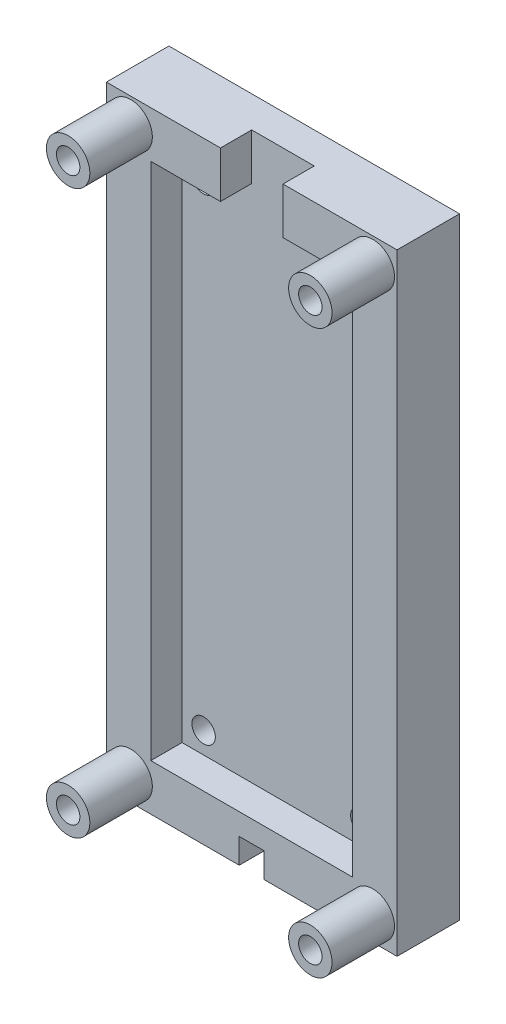
SolidWorks part; units mm, degrees
ref_plane "Front Plane" through (0, 0, 0) normal (0, 0, 1) x (1, 0, 0)
ref_plane "Top Plane" through (0, 0, 0) normal (0, 1, 0) x (1, 0, 0)
ref_plane "Right Plane" through (0, 0, 0) normal (1, 0, 0) x (0, 0, -1)
sketch "Sketch2" plane through (0, 0, 0) normal (0, 0, 1) x (1, 0, 0)
  line L0 (-7.1, -7.425) -> (-7.1, 90.475)
  line L1 (0, 0) -> (32.3, 0)
  line L2 (0, 0) -> (0, 83.05)
  line L3 (0, 83.05) -> (32.3, 83.05)
  line L4 (32.3, 0) -> (32.3, 83.05)
  line L5 (0, 0) -> (32.3, 83.05) construction
  line L6 (0, 83.05) -> (32.3, 0) construction
  line L7 (-7.1, 90.475) -> (39.4, 90.475)
  line L8 (39.4, -7.425) -> (39.4, 90.475)
  line L9 (-7.1, -7.425) -> (39.4, -7.425)
  line L10 (16.15, 3.425) -> (16.15, 79.625) construction
  line L11 (3.45, 79.625) -> (28.85, 79.625)
  line L12 (3.45, 79.625) -> (3.45, 3.425)
  line L13 (3.45, 3.425) -> (28.85, 3.425)
  line L14 (28.85, 79.625) -> (28.85, 3.425)
  line L15 (3.45, 79.625) -> (28.85, 3.425) construction
  line L16 (3.45, 3.425) -> (28.85, 79.625) construction
  line L17 (16.15, 0) -> (16.15, -7.425) construction
  line L18 (0, 41.525) -> (-7.1, 41.525) construction
  point P4 (16.15, 41.525)
  point P10 (16.15, 41.525)
  dimension "D1" = 83.05
  dimension "D2" = 32.3
  dimension "D4" = 25.4
  dimension "D5" = 76.2
  dimension "D3" = 46.5
  dimension "D6" = 97.9
extrude "Boss-Extrude1" add sketch "Sketch2" along normal mid plane 10 contours L0 L9 L8 L7 L4 L1 L2 L3 region at (-6.0162, 41.525, 0)
extrude "Boss-Extrude2" add sketch "Sketch2<4>" against normal blind 5 contours L14 L11 L12 L13 | L1 L4 L3 L2 L11 L14 L13 L12 region at (0.8911, 41.525, 0) region at (16.15, 41.525, 0)
sketch "Sketch2<4>" plane through (0, 0, 0) normal (0, 0, 1) x (1, 0, 0) same geometry as "Sketch2"
ref_axis "Axis1" through (16.15, 3.425, 0) along (0, 1, 0)
sketch "Sketch3" plane through (-7.1, 0, 0) normal (-1, 0, 0) x (0, 0, 1)
  line L0 (-5, -7.425) -> (-5, 90.475) construction
  line L1 (-5, 76.725) -> (5, 76.725)
  line L2 (-5, 76.725) -> (-5, 74.225)
  line L3 (-5, 74.225) -> (5, 74.225)
  line L4 (5, 76.725) -> (5, 74.225)
  line L5 (-5, 76.725) -> (5, 74.225) construction
  line L6 (-5, 74.225) -> (5, 76.725) construction
  line L7 (5, -7.425) -> (5, 90.475) construction
  line L8 (-5, 41.525) -> (5, 41.525) construction
  line L9 (-5, 8.825) -> (5, 8.825)
  line L10 (5, 6.325) -> (5, 8.825)
  line L11 (-5, 6.325) -> (5, 6.325)
  line L12 (-5, 6.325) -> (-5, 8.825)
  line L14 (5, 90.475) -> (-5, 90.475) construction
  point P4 (0, 75.475)
  dimension "D1" = 2.5
  dimension "D2" = 15
extrude "Boss-Extrude3" [suppressed] add sketch "Sketch3" along normal blind 2.5
ref_plane "Plane1" through (16.15, 0, 0) normal (-1, 0, 0) x (0, 0, 1)
chamfer "Chamfer1" [suppressed] distance 0.5 angle 45
mirror "Mirror2" [suppressed] about plane through (16.15, 0, 0) normal (-1, 0, 0)
sketch "Sketch4" plane through (0, 0, 0) normal (0, 0, 1) x (1, 0, 0)
  point P0 (3.45, 79.625)
  point P3 (28.85, 79.625)
  point P6 (3.45, 3.425)
  point P9 (28.85, 3.425)
hole_wizard "Tap Drill for M3x0.5 Tap1" positions "Sketch4" profile "Sketch5" hole size "M3x0.5" standard "ANSI Metric" end condition through all
sketch "Sketch5" plane through (3.45, 79.625, 0) normal (1, 0, 0) x (0, -1, 0)
  line L0 (0, 0) -> (0, 5)
  line L1 (0, 5) -> (1.875, 5)
  line L2 (1.875, 5) -> (1.875, 0)
  line L5 (1.875, 0) -> (0, 0)
  line L11 (0, -6.35) -> (0, 107.95) construction
  dimension "Thru Hole Dia." = 3.75
  dimension "Thru Hole Depth" = 5
sketch "Sketch7" plane through (0, 0, 0) normal (0, 0, 1) x (1, 0, 0)
  line L0 (16.15, 5.5) -> (16.15, -5.5) construction
  line L1 (-3.225, 86.525) -> (35.525, 86.525)
  line L2 (-3.225, 86.525) -> (-3.225, -3.475)
  line L3 (-3.225, -3.475) -> (35.525, -3.475)
  line L4 (35.525, 86.525) -> (35.525, -3.475)
  line L5 (16.15, -3.475) -> (16.15, 86.525) construction
  line L6 (-3.225, 41.525) -> (35.525, 41.525) construction
  line L7 (9.5243, 83.05) -> (9.5243, 86.525) construction
  line L8 (0, 83.05) -> (32.3, 83.05) construction
  line L9 (9.5243, -3.475) -> (9.5243, 0) construction
  line L10 (0, 0) -> (32.3, 0) construction
  circle A0 centre (-3.225, 86.525) radius 1.875
  circle A1 centre (35.525, 86.525) radius 1.875
  circle A2 centre (35.525, -3.475) radius 1.875
  circle A3 centre (-3.225, -3.475) radius 1.875
  circle A4 centre (-3.225, 86.525) radius 3.475
  circle A5 centre (35.525, 86.525) radius 3.475
  circle A6 centre (-3.225, -3.475) radius 3.475
  circle A7 centre (35.525, -3.475) radius 3.475
  point P480 (16.15, 41.525)
  dimension "D4" = 3.75
  dimension "D1" = 38.75
  dimension "D2" = 90
  dimension "D3" = 9.5243
  dimension "D5" = 1.6
extrude "Boss-Extrude5" add sketch "Sketch7" along normal blind 15 contours L2 A6 L3 A3 | L3 A6 L2 A3 | A4 | A0 | A5 | A1 | A2 | A7 region at (-1.4713, -1.7213, 0) region at (-3.3233, -0.8, 0)
sketch "Sketch6" plane through (0, 90.475, 0) normal (0, 1, 0) x (1, 0, 0)
  line L4 (-12.2839, -5.4418) -> (-12.3348, -5.4418)
  line L5 (44.5642, -5.5441) -> (44.6151, -5.5441)
  arc A0 (44.6151, -5.5441) -> (-12.3348, -5.4418) centre (16.15, 0) cw
  arc A1 (44.5642, -5.5441) -> (-12.2839, -5.4418) centre (16.15, 0) cw
  arc A2 (44.566, -5.5346) -> (-12.2857, -5.4325) centre (16.15, 0) cw construction
  dimension "D1" = 29
  dimension "D2" = 0.05
extrude "Boss-Extrude4" add sketch "Sketch6" against normal blind 97.55 separate body
extrude "Cut-Extrude1" cut sketch "Sketch6<2>" against normal through all both and the other way through all
sketch "Sketch6<2>" plane through (0, 90.475, 0) normal (0, 1, 0) x (1, 0, 0) same geometry as "Sketch6"
sketch "Sketch11" plane through (0, 0, 5) normal (0, 0, 1) x (1, 0, 0)
  line L0 (0, 83.05) -> (32.3, 83.05) construction
  line L1 (11.15, 75.55) -> (21.15, 75.55)
  line L2 (11.15, 75.55) -> (11.15, 90.55)
  line L3 (11.15, 90.55) -> (21.15, 90.55)
  line L4 (21.15, 75.55) -> (21.15, 90.55)
  line L5 (11.15, 75.55) -> (21.15, 90.55) construction
  line L6 (11.15, 90.55) -> (21.15, 75.55) construction
  point P0 (16.15, 83.05)
  dimension "D1" = 10
  dimension "D2" = 15
extrude "Cut-Extrude2" cut sketch "Sketch11" against normal up to surface (5 mm away) and the other way through all up to face at (5.325, 79.625, 0)
sketch "Sketch12" plane through (0, 0, 5) normal (0, 0, 1) x (1, 0, 0)
  line L0 (-7.1, -7.425) -> (39.4, -7.425) construction
  line L1 (18.15, -11.425) -> (14.15, -11.425)
  line L2 (18.15, -11.425) -> (18.15, -3.425)
  line L3 (18.15, -3.425) -> (14.15, -3.425)
  line L4 (14.15, -11.425) -> (14.15, -3.425)
  line L5 (18.15, -11.425) -> (14.15, -3.425) construction
  line L6 (18.15, -3.425) -> (14.15, -11.425) construction
  point P0 (16.15, -7.425)
  dimension "D1" = 8
  dimension "D2" = 4
extrude "Cut-Extrude3" cut sketch "Sketch12" against normal through all
